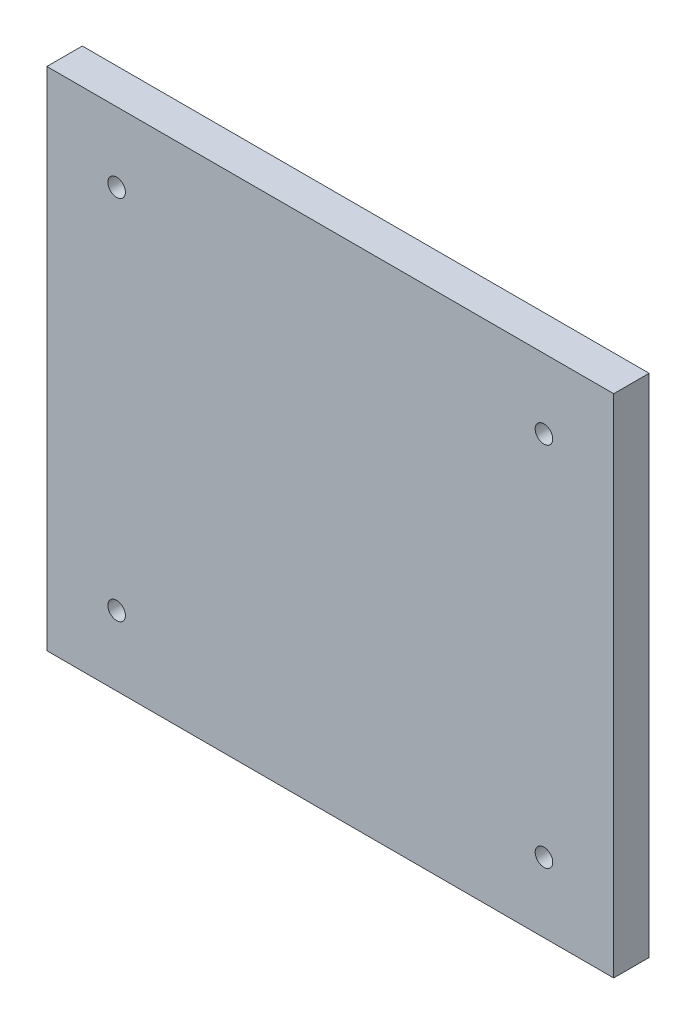
SolidWorks part; units mm, degrees
ref_plane "Top Plane" through (0, 0, 0) normal (0, 0, 1) x (1, 0, 0)
ref_plane "Front Plane" through (0, 0, 0) normal (0, 1, 0) x (1, 0, 0)
ref_plane "Right Plane" through (0, 0, 0) normal (1, 0, 0) x (0, 0, -1)
sketch "Profile Sketch" plane through (0, 0, 0) normal (0, 0, 1) x (1, 0, 0)
  line L1 (-50.8, -45.35) -> (50.8, -45.35)
  line L2 (-50.8, -45.35) -> (-50.8, 45.35)
  line L3 (-50.8, 45.35) -> (50.8, 45.35)
  line L4 (50.8, -45.35) -> (50.8, 45.35)
  line L5 (-50.8, -45.35) -> (50.8, 45.35) construction
  line L6 (-50.8, 45.35) -> (50.8, -45.35) construction
  point P0 (0, 0)
  dimension "D1" = 90.7
  dimension "D2" = 101.6
extrude "Profile Extrude" add sketch "Profile Sketch" along normal blind 6.35
sketch "Mounting Hole Sketch" plane through (0, 0, 6.35) normal (0, 0, 1) x (1, 0, 0)
  line L0 (50.8, 45.35) -> (-50.8, 45.35) construction
  line L1 (0, 0) -> (0, 45.35) construction
  line L2 (0, 0) -> (-50.8, 0) construction
  line L3 (-50.8, 45.35) -> (-50.8, -45.35) construction
  circle A0 centre (-38.3, 32.85) radius 1.575
  circle A1 centre (38.3, 32.85) radius 1.575
  circle A2 centre (38.3, -32.85) radius 1.575
  circle A3 centre (-38.3, -32.85) radius 1.575
  dimension "D1" = 3.15
  dimension "D2" = 12.5
  dimension "D3" = 12.5
extrude "Mounting Hole Cut" cut sketch "Mounting Hole Sketch" against normal through all
equation "\"D3@Mounting Hole Sketch\"=\"D2@Mounting Hole Sketch\""
